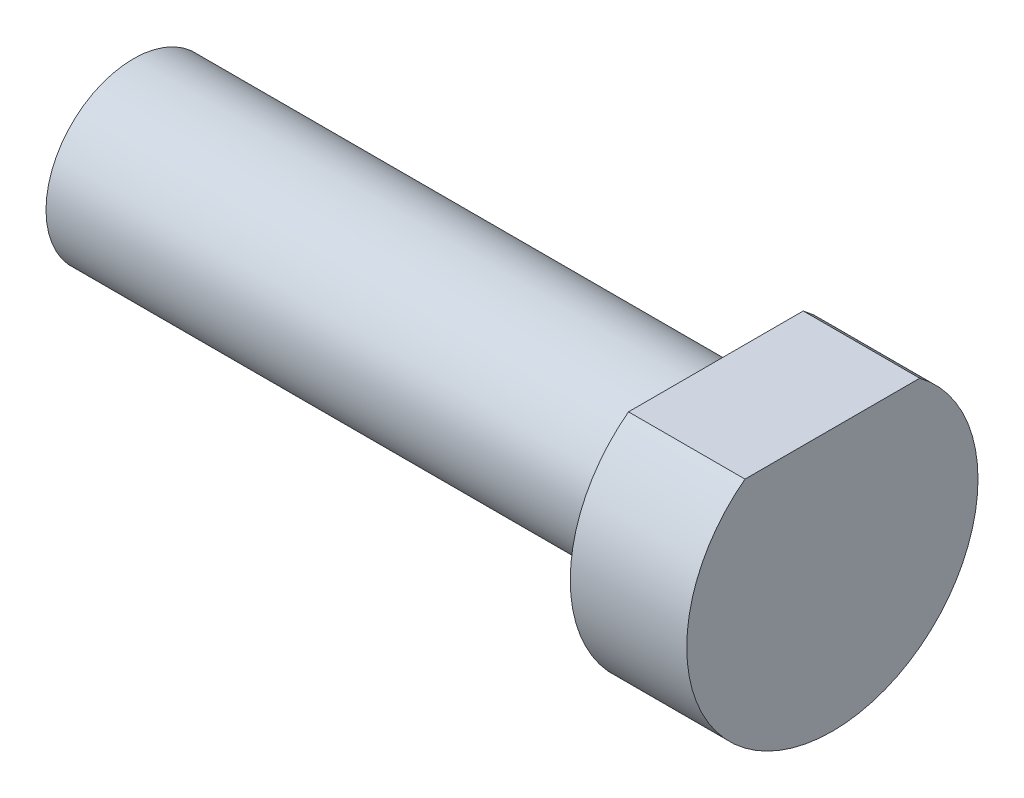
SolidWorks part; units mm, degrees
ref_plane "Front Plane" through (0, 0, 0) normal (0, 0, 1) x (1, 0, 0)
ref_plane "Top Plane" through (0, 0, 0) normal (0, 1, 0) x (1, 0, 0)
ref_plane "Right Plane" through (0, 0, 0) normal (1, 0, 0) x (0, 0, -1)
sketch "Sketch1" plane through (0, 0, 0) normal (0, 0, 1) x (1, 0, 0)
  line L0 (0, 0) -> (0, -1.5)
  line L1 (0, -1.5) -> (10, -1.5)
  line L2 (10, -1.5) -> (10, -2.5)
  line L5 (12, 0) -> (0, 0)
  line L6 (10, -2.5) -> (12, -2.5)
  line L7 (12, -2.5) -> (12, 0)
  dimension "D1" = 10
  dimension "D2" = 2
  dimension "D3" = 2.5
  dimension "D4" = 1.5
revolve "Revolve1" add sketch "Sketch1" angle 360 about L5
ref_plane "Plane1" through (0, 3, 0) normal (0, 1, 0) x (1, 0, 0)
sketch "Sketch2" plane through (0, 3, 0) normal (0, 1, 0) x (1, 0, 0)
  line L1 (10, 2.5) -> (12, 2.5)
  line L2 (10, 2.5) -> (10, -2.5)
  line L3 (10, -2.5) -> (12, -2.5)
  line L4 (12, 2.5) -> (12, -2.5)
extrude "Cut-Extrude1" cut sketch "Sketch2" against normal blind 1
